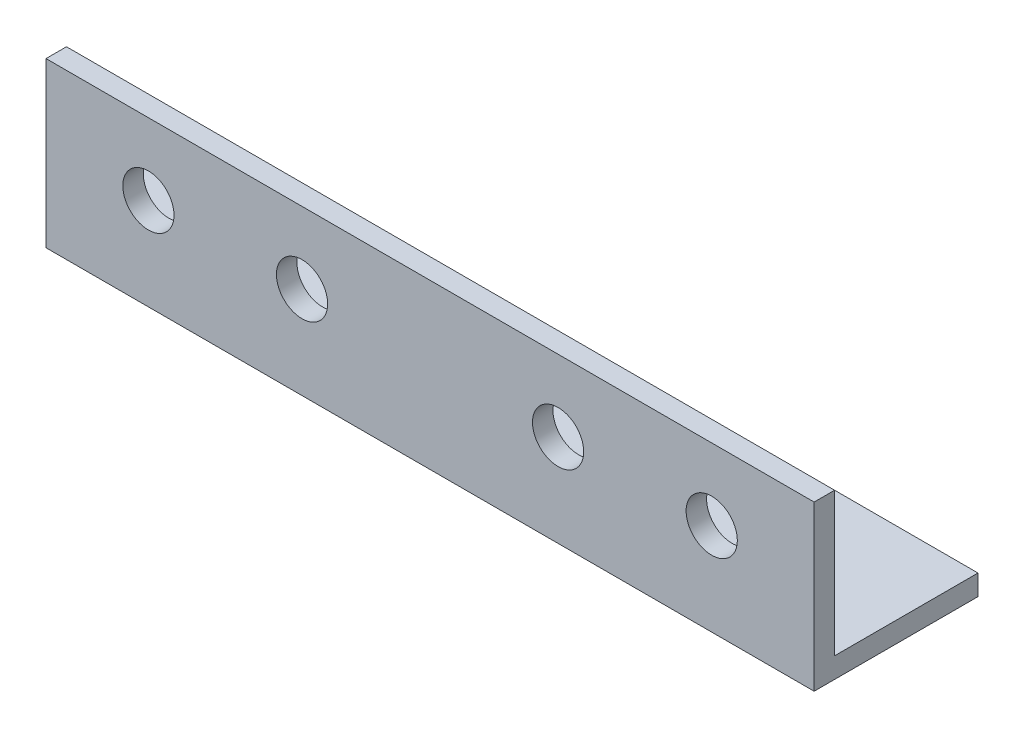
SolidWorks part; units mm, degrees
ref_plane "Спереди" through (0, 0, 0) normal (0, 0, 1) x (1, 0, 0)
ref_plane "Сверху" through (0, 0, 0) normal (0, 1, 0) x (1, 0, 0)
ref_plane "Справа" through (0, 0, 0) normal (1, 0, 0) x (0, 0, -1)
sketch "Эскиз1" plane through (0, 0, 0) normal (1, 0, 0) x (0, 0, -1)
  line L0 (0, 32) -> (0, 0)
  line L1 (0, 0) -> (32, 0)
extrude "Вытянуть-Тонкостенный1" add sketch "Эскиз1" along normal blind 150 thin thin type one direction reverse wall 4
sketch "Эскиз2" plane through (0, 0, -4) normal (0, 0, -1) x (-1, 0, 0)
  line L2 (-75, 33.9302) -> (-75, -4.466) construction
  line L3 (-75, -6) -> (-75, 0) construction
  circle A0 centre (-130, 18) radius 5
  circle A1 centre (-100, 18) radius 5
  circle A2 centre (-50, 18) radius 5
  circle A3 centre (-20, 18) radius 5
  dimension "D1" = 2
extrude "Вырез-Вытянуть1" cut sketch "Эскиз2" against normal through all
